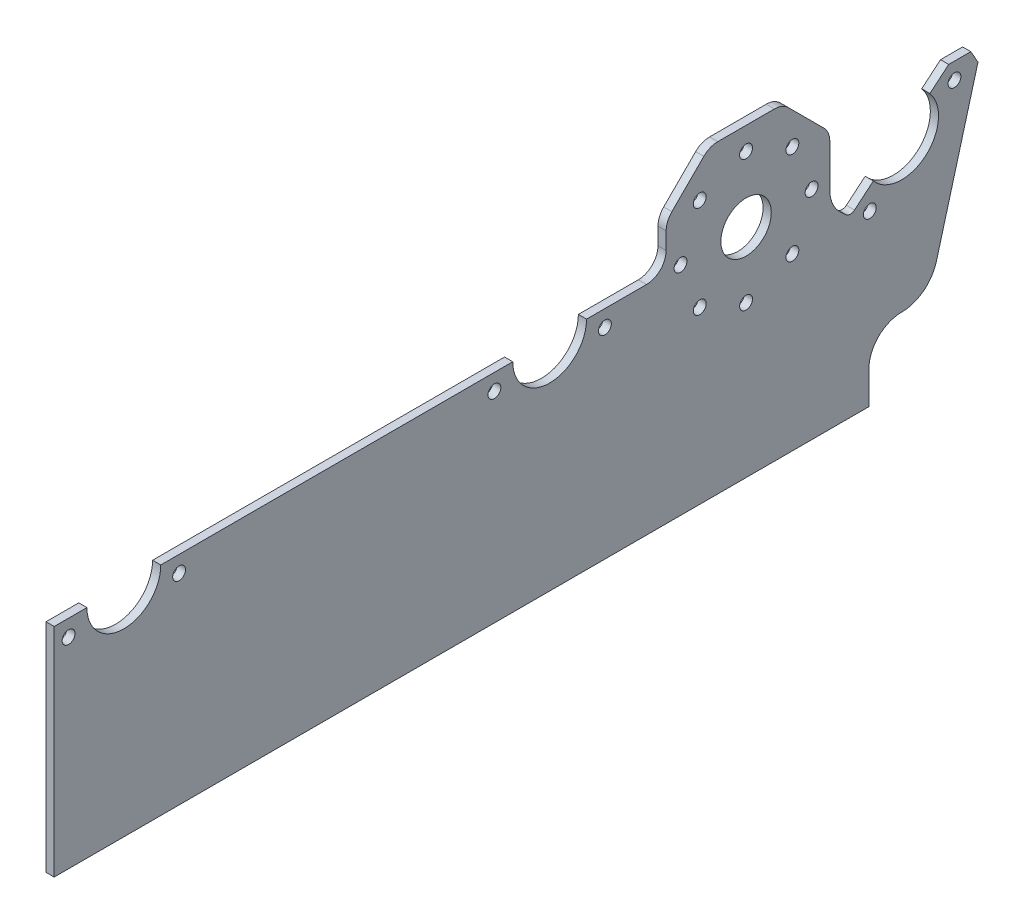
SolidWorks part; units mm, degrees
material "6061 Alloy"
ref_plane "Front Plane" through (0, 0, 0) normal (0, 0, 1) x (1, 0, 0)
ref_plane "Top Plane" through (0, 0, 0) normal (0, 1, 0) x (1, 0, 0)
ref_plane "Right Plane" through (0, 0, 0) normal (1, 0, 0) x (0, 0, -1)
sketch "Sketch1" plane through (0, 0, 0) normal (1, 0, 0) x (0, 0, -1)
  line L0 (-12.7, -12.7) -> (-328.6379, -12.7)
  line L1 (-328.6379, -12.7) -> (-328.6379, 71.4629)
  line L2 (-328.6379, 71.4629) -> (-315.9379, 71.4629)
  line L3 (-287.3121, 71.4629) -> (-150.8125, 71.4629)
  line L5 (10.9643, 80.6631) -> (18.2626, 86.7871)
  line L7 (-328.6379, 12.7) -> (13.4731, 12.7) construction
  line L8 (-12.7, -12.7) -> (-12.7, 0)
  line L9 (0, 12.4079) -> (0, 12.7) construction
  line L10 (13.4731, 22.9772) -> (30.9626, 86.7871)
  line L12 (-10.9643, 62.2627) -> (10.9643, 80.6631) construction
  line L13 (18.2626, 86.7871) -> (30.9626, 86.7871)
  line L14 (-122.1867, 71.4629) -> (-91.313, 71.4629)
  line L15 (-10.9643, 62.2627) -> (-18.2626, 56.1387)
  line L16 (-21.6532, 56.2511) -> (-23.945, 58.4485)
  line L18 (0, 71.4629) -> (-136.4996, 71.4629) construction
  line L19 (-328.6379, 15.875) -> (13.4731, 15.875) construction
  line L20 (-27.8553, 67.6154) -> (-27.8553, 87.307)
  line L21 (-27.8553, 87.307) -> (-46.1742, 105.6259)
  line L22 (-46.1742, 105.6259) -> (-74.4758, 105.6259)
  line L23 (-91.313, 88.7887) -> (-91.313, 71.4629)
  line L25 (-74.4758, 105.6259) -> (-91.313, 88.7887)
  arc A3 (0, 12.7) -> (13.4731, 22.9772) centre (0, 26.67) ccw
  arc A4 (0, 12.7) -> (-12.7, 0) centre (0, 0) ccw
  circle A5 centre (0, 0) radius 12.4079 construction
  arc A6 (-315.9379, 71.4629) -> (-287.3121, 71.4629) centre (-301.625, 71.4629) ccw
  arc A7 (-150.8125, 71.4629) -> (-122.1867, 71.4629) centre (-136.4996, 71.4629) ccw
  arc A8 (-10.9643, 62.2627) -> (10.9643, 80.6631) centre (0, 71.4629) ccw
  arc A9 (-18.2626, 56.1387) -> (-21.6532, 56.2511) centre (-19.8953, 58.0845) cw
  circle A11 centre (-60.325, 71.4629) radius 9.779
  arc A14 (-27.8553, 67.6154) -> (-23.945, 58.4485) centre (-15.1553, 67.6154) ccw
  circle A15 centre (-60.325, 71.4629) radius 25.4 construction
  circle A16 centre (-60.325, 96.8629) radius 2.413
  circle A17 centre (-42.3645, 89.4234) radius 2.413
  circle A18 centre (-34.925, 71.4629) radius 2.413
  circle A19 centre (-42.3645, 53.5024) radius 2.413
  circle A20 centre (-60.325, 46.0629) radius 2.413
  circle A21 centre (-78.2855, 53.5024) radius 2.413
  circle A22 centre (-85.725, 71.4629) radius 2.413
  circle A23 centre (-78.2855, 89.4234) radius 2.413
  point P4 (-170.669, -12.7)
  point P44 (-82.018, 71.4629)
  point P51 (-27.8553, 62.1979)
  point P60 (-60.325, 71.4629)
  dimension "D1" = 25.4
  dimension "D3" = 12.7
  dimension "D5" = 28.6258
  dimension "D6" = 3.175
  dimension "D7" = 13.97
  dimension "D8" = 12.7
  dimension "D10" = 24.8158
  dimension "D13" = 9.5273
  dimension "D14" = 140
  dimension "D15" = 2.54
  dimension "D16" = 50.8
  dimension "D17" = 60.325
  dimension "D18" = 41.275
  dimension "D24" = 3.175
  dimension "D26" = 12.7
  dimension "D19" = 4.826
  dimension "D25" = 6.35
  dimension "D29" = 6.35
  dimension "D20" = 4.6567
  dimension "D30" = 9.779
  dimension "D2" = 0
  dimension "D4" = 12.7
  dimension "D9" = 12.7
  dimension "D11" = 301.625
  dimension "D12" = 301.625
  dimension "D21" = 8
  dimension "D22" = 45
  dimension "D23" = 45
  dimension "D27" = 6.35
  dimension "D28" = 3.175
extrude "Boss-Extrude1" add sketch "Sketch1" along normal blind 3.175
hole_wizard "#10 Clearance Hole1" positions "Sketch2" profile "Sketch3" hole size "#10" standard "ANSI Inch" end condition through all
sketch "Sketch2" plane through (3.175, 0, 0) normal (1, 0, 0) x (0, 0, -1)
  line L0 (-323.0562, 65.1129) -> (-280.1937, 65.1129) construction
  line L2 (-157.9309, 65.1129) -> (-115.0683, 65.1129) construction
  line L4 (-12.3356, 52.8228) -> (20.499, 80.3743) construction
  line L6 (-315.9379, 71.4629) -> (-328.6379, 71.4629) construction
  line L7 (-301.625, 65.1129) -> (-301.625, 71.4629) construction
  line L9 (-136.4996, 71.4629) -> (-136.4996, 65.1129) construction
  line L11 (0, 71.4629) -> (4.0817, 66.5985) construction
  line L14 (18.2626, 86.7871) -> (10.9643, 80.6631) construction
  line L15 (18.2626, 86.7871) -> (10.9643, 80.6631) construction
  point P0 (-323.0562, 65.1129)
  point P2 (-280.1938, 65.1129)
  point P4 (-157.9309, 65.1129)
  point P6 (-115.0683, 65.1129)
  point P8 (-12.3356, 52.8228)
  point P10 (20.499, 80.3743)
  dimension "D1" = 42.8625
  dimension "D2" = 6.35
  dimension "D3" = 6.35
sketch "Sketch3" plane through (3.175, 65.1129, 323.0562) normal (0, 1, 0) x (0, 0, -1)
  line L0 (0, 0) -> (0, 3.175)
  line L1 (0, 3.175) -> (2.4892, 3.175)
  line L2 (2.4892, 3.175) -> (2.4892, 0)
  line L5 (2.4892, 0) -> (0, 0)
  line L11 (0, -6.35) -> (0, 107.95) construction
  dimension "Thru Hole Dia." = 4.9784
  dimension "Thru Hole Depth" = 3.175
hole_wizard "#10 Clearance Hole2" positions "Sketch5" profile "Sketch6" hole size "#10" standard "ANSI Inch"
sketch "Sketch5" plane through (3.175, 0, 0) normal (1, 0, 0) x (0, 0, -1)
  point P0 (-60.325, 96.8629)
  point P3 (-42.3645, 89.4234)
  point P6 (-34.925, 71.4629)
  point P9 (-42.3645, 53.5024)
  point P12 (-60.325, 46.0629)
  point P15 (-78.2855, 53.5024)
  point P18 (-85.725, 71.4629)
  point P21 (-78.2855, 89.4234)
sketch "Sketch6" plane through (3.175, 96.8629, 60.325) normal (0, 1, 0) x (0, 0, -1)
  line L0 (0, 0) -> (0, 4.6707)
  line L1 (0, 4.6707) -> (2.4892, 3.175)
  line L2 (2.4892, 3.175) -> (2.4892, 0)
  line L5 (2.4892, 0) -> (0, 0)
  line L10 (0, 4.6707) -> (-2.4892, 3.175) construction
  line L11 (0, -6.35) -> (0, 107.95) construction
  dimension "Hole Dia." = 4.9784
  dimension "Hole Depth" = 3.175
  dimension "Drill Angle" = 118
chamfer "Chamfer1" distance 5.08 angle 45 1 edges at (1.5875, 86.7871, -30.9626) first distance on face at (1.5875, 54.8821, -22.2179)
fillet "Fillet1" radius 7.62 5 edges at (1.5875, 87.307, 27.8553) (1.5875, 105.6259, 46.1742) (1.5875, 105.6259, 74.4758) (1.5875, 88.7887, 91.313) (1.5875, 71.4629, 91.313)
